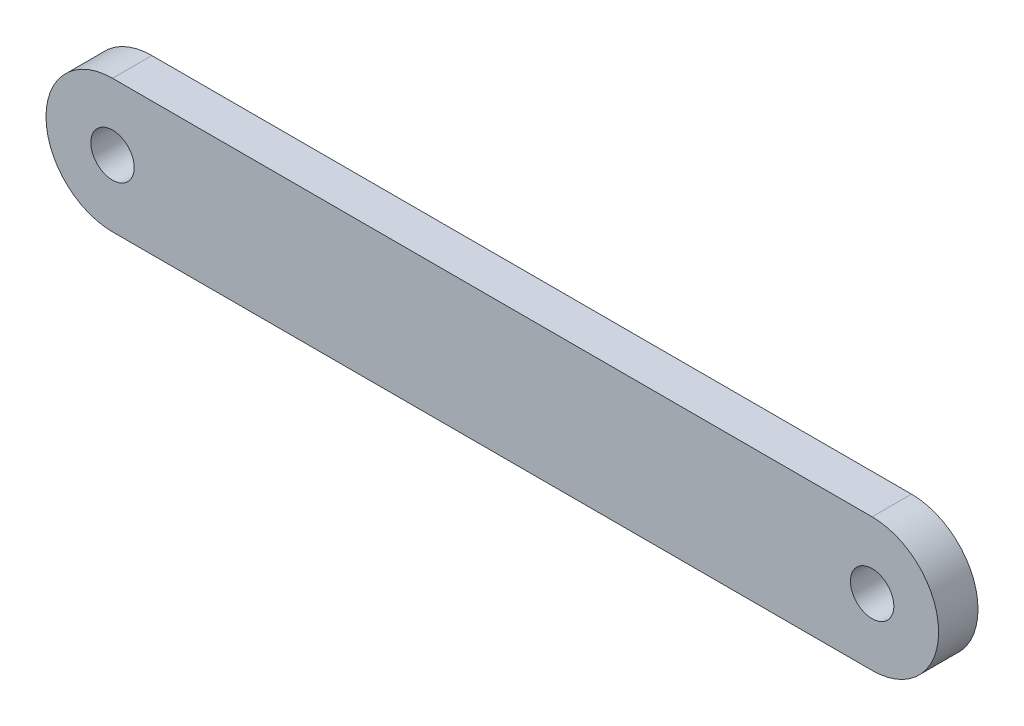
SolidWorks part; units mm, degrees
material "ABS"
ref_plane "Front Plane" through (0, 0, 0) normal (0, 0, 1) x (1, 0, 0)
ref_plane "Top Plane" through (0, 0, 0) normal (0, 1, 0) x (1, 0, 0)
ref_plane "Right Plane" through (0, 0, 0) normal (1, 0, 0) x (0, 0, -1)
sketch "Sketch2" plane through (0, 0, 0) normal (0, 0, -1) x (-1, 0, 0)
  line L0 (-30.6292, 48.8236) -> (30.6292, 48.8236) construction
  line L1 (-30.6292, 54.1878) -> (30.6292, 54.1878)
  line L2 (-30.6292, 43.4594) -> (30.6292, 43.4594)
  arc A0 (-30.6292, 54.1878) -> (-30.6292, 43.4594) centre (-30.6292, 48.8236) ccw
  arc A1 (30.6292, 43.4594) -> (30.6292, 54.1878) centre (30.6292, 48.8236) ccw
  arc A2 (54.5148, -31.5775) -> (-54.5148, -31.5775) centre (0, 0) ccw construction
  circle A3 centre (-30.6292, 48.8236) radius 1.75
  circle A4 centre (30.6292, 48.8236) radius 1.75
  point P4 (0, 48.8236)
  dimension "D1" = 3.5
extrude "Boss-Extrude1" add sketch "Sketch2" along normal blind 3.175
